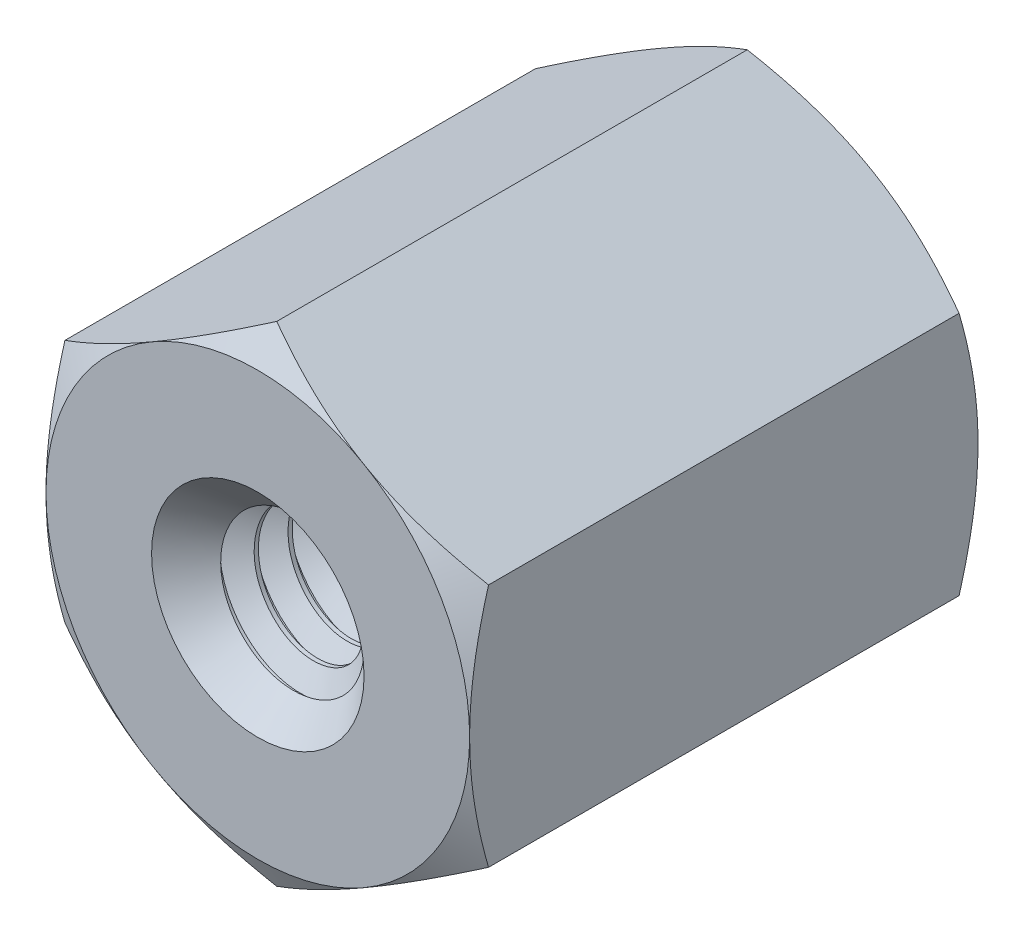
SolidWorks part; units mm, degrees
material "Brass"
ref_plane "Front Plane" through (0, 0, 0) normal (0, 0, 1) x (1, 0, 0)
ref_plane "Top Plane" through (0, 0, 0) normal (0, 1, 0) x (1, 0, 0)
ref_plane "Right Plane" through (0, 0, 0) normal (1, 0, 0) x (0, 0, -1)
sketch "Sketch1" plane through (0, 0, 0) normal (0, 0, 1) x (1, 0, 0)
  line L1 (0, 2.8868) -> (-2.5, 1.4434)
  line L2 (-2.5, 1.4434) -> (-2.5, -1.4434)
  line L3 (-2.5, -1.4434) -> (0, -2.8868)
  line L4 (0, -2.8868) -> (2.5, -1.4434)
  line L5 (2.5, -1.4434) -> (2.5, 1.4434)
  line L6 (2.5, 1.4434) -> (0, 2.8868)
  circle A0 centre (0, 0) radius 2.5 construction
  dimension "Hex" = 5
extrude "Extrude1" add sketch "Sketch1" against normal blind 6
sketch "Sketch2" plane through (0, 0, 0) normal (0, 0, 1) x (1, 0, 0)
  circle A0 centre (0, 0) radius 2.5 construction
  circle A1 centre (0, 0) radius 2.5
extrude "Cut-Extrude1" cut sketch "Sketch2" against normal through all draft 60 flip side to cut
sketch "Sketch3" plane through (0, 0, -6) normal (0, 0, -1) x (-1, 0, 0)
  circle A1 centre (0, 0) radius 2.5
  circle A2 centre (0, 0) radius 2.5
  dimension "D1" = 0
extrude "Cut-Extrude2" cut sketch "Sketch3" against normal through all draft 60 flip side to cut
sketch "Sketch4" plane through (0, 0, 0) normal (0, 0, 1) x (1, 0, 0)
  circle A0 centre (0, 0) radius 1
  dimension "Thread Dia" = 2
extrude "Cut-Extrude3" cut sketch "Sketch4" against normal through all
sketch "Sketch7" plane through (0, 0, 0) normal (0, 0, 1) x (1, 0, 0)
  circle A4 centre (0, 0) radius 1.254
  circle A5 centre (0, 0) radius 1.254
  dimension "D1" = 0.254
sketch "Sketch8" plane through (0, 0, -6) normal (0, 0, -1) x (-1, 0, 0)
  circle A1 centre (0, 0) radius 1.254
  circle A2 centre (0, 0) radius 1.254 construction
sketch "Sketch5" plane through (0, 0, 0) normal (0, 0, 1) x (1, 0, 0)
  circle A0 centre (0, 0) radius 1 construction
  circle A1 centre (0, 0) radius 1
curve "Helix/Spiral1" pitch 0.4 height 6.4 radius 1 centre (0, 0, 0) axis (0, 0, -1) start towards (0, 1, 0) parameters "pitch"=0.4
sketch "Sketch9" plane through (0, 0, 0) normal (1, 0, 0) x (0, 0, -1)
  line L0 (-0.2, 1) -> (-0.15, 1)
  line L1 (-0.15, 1) -> (0, 0.7402)
  line L2 (-0.2, 1) -> (-0.35, 0.7402)
  line L3 (-0.35, 0.7402) -> (0, 0.7402)
  line L4 (-0.175, 1) -> (-0.175, 0.7402) construction
  line L5 (-0.275, 0.8701) -> (-0.075, 0.8701) construction
  line L7 (0, 0.7402) -> (0, 1) construction
  line L8 (0, 1) -> (0, -1) construction
  dimension "D1" = 0.05
  dimension "D2" = 0.2
  dimension "D3" = 60
sketch "Sketch12" plane through (0, 0, 0) normal (0, 0, 1) x (1, 0, 0)
  circle A0 centre (0, 0) radius 0.7402
  circle A1 centre (0, 0) radius 1 construction
  circle A2 centre (0, 0) radius 1
extrude "Extrude2" add sketch "Sketch12" against normal up to surface (6 mm away) up to face at (1, 0, -6)
sweep "Cut-Sweep1" cut profiles "Sketch9" path "Helix/Spiral1" align with end faces yes
extrude "Cut-Extrude6" cut sketch "Sketch7" against normal through all draft 45
extrude "Cut-Extrude7" cut sketch "Sketch8" against normal through all draft 45
equation "\"D2@Sketch9\" = \"pitch@Helix/Spiral1\"*.5"
equation "\"D3@Helix/Spiral1\" = \"pitch@Helix/Spiral1\"+\"Height@Extrude1\""
equation "\"D1@Sketch9\" = \"pitch@Helix/Spiral1\"*.125"
